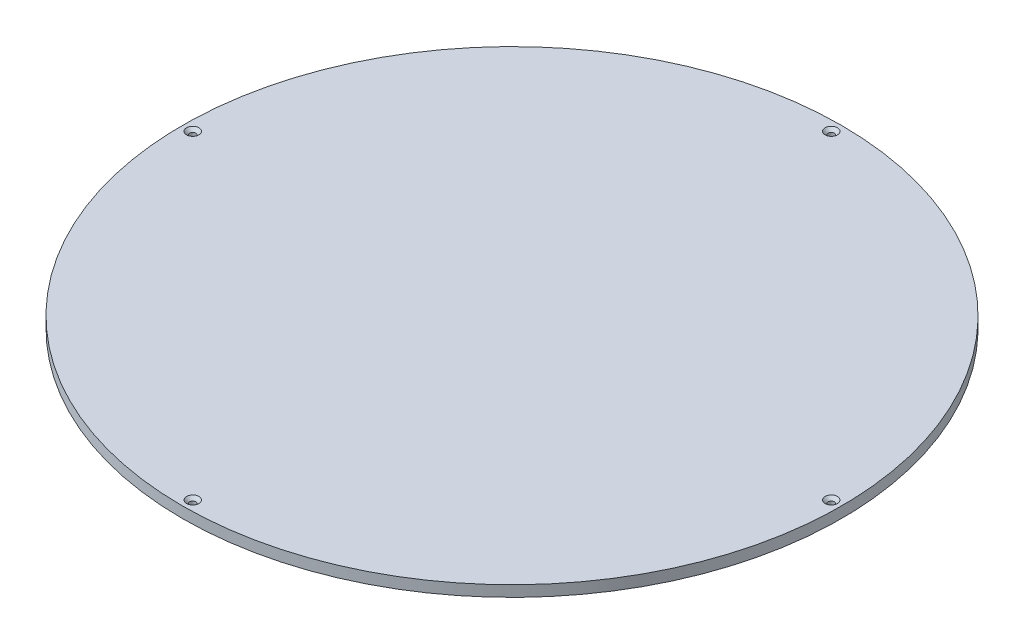
SolidWorks part; units mm, degrees
material "Pine"
ref_plane "Front Plane" through (0, 0, 0) normal (0, 0, 1) x (1, 0, 0)
ref_plane "Top Plane" through (0, 0, 0) normal (0, 1, 0) x (1, 0, 0)
ref_plane "Right Plane" through (0, 0, 0) normal (1, 0, 0) x (0, 0, -1)
sketch "Sketch1" plane through (0, 0, 0) normal (0, 1, 0) x (1, 0, 0)
  line L0 (-8.7941, 0) -> (197.1788, 0) construction
  circle A0 centre (0, 0) radius 160
  circle A1 centre (155, 0) radius 1.5
  circle A2 centre (0, -155) radius 1.5
  circle A3 centre (-155, 0) radius 1.5
  circle A4 centre (0, 155) radius 1.5
  point P16 (0, 0)
  dimension "D1" = 320
  dimension "D2" = 3
  dimension "D3" = 155
  dimension "D4" = 4
extrude "Boss-Extrude1" add sketch "Sketch1" against normal blind 5.333
chamfer "Chamfer1" distance 1.5 angle 45 4 edges at (155, 0, 1.5) (-155, 0, 1.5) (0, 0, -153.5) (0, 0, 156.5)
equation "\"rod_diameter\"= 8"
equation "\"rod_hole_thickness\"= 4"
equation "\"rod_radius\"= \"rod_diameter\" / 2"
equation "\"platter_diameter\"= 320"
equation "\"platter_radius\"= \"platter_diameter\" / 2"
equation "\"extruder_mount_hole_spacing\"= 75"
equation "\"arm_rod_spacing\"= 40"
equation "\"motor_level_rod_spacing\"= 15"
equation "\"linear_bearing_diameter\"= 15"
equation "\"z_rod_spacing\"= 75"
equation "\"platter_rod_spacing\"= 50"
equation "\"rod_nut_thickness\"= 6.5"
equation "\"rod_nut_inscribed_diameter\"= 13"
equation "\"z_height\"= 400"
equation "\"D1@Sketch1\"=\"platter_diameter\""
equation "\"D3@Sketch1\"=\"platter_radius\"-5"
equation "\"top_frame_spacing\"= 90"
equation "\"z_drive_rod_offset\"= 12"
equation "\"gear_pitch\"=2"
equation "\"r_gear_teeth\"= 450"
equation "\"theta_gear_teeth\"= 385"
equation "\"sheet_thickness\"=5.333"
equation "\"sheet_tab_hole_thickness\"= \"sheet_thickness\""
equation "\"sheet_tab_width\"= \"sheet_thickness\"*2"
equation "\"sheet_double_tab_width\"= 35"
equation "\"sheet_bolt_diameter\"= 3"
equation "\"sheet_bolt_length\"= 16"
equation "\"sheet_nut_diameter\"= 5.5"
equation "\"sheet_nut_thickness\"= 2.5"
equation "\"sheet_nut_depth\"= 10"
equation "\"bearing_outside_diameter\"= 22"
equation "\"bearing_thickness\"= 7"
equation "\"corner_part_thickness\"= \"sheet_thickness\" + \"bearing_thickness\""
equation "\"setscrew_nut_diameter\"= 6"
equation "\"setscrew_nut_thickness\"= 3"
equation "\"setscrew_bolt_diameter\"= 3"
equation "\"motor_shaft_diameter\"= 5.7"
equation "\"D1@Boss-Extrude1\"= \"sheet_thickness\""
